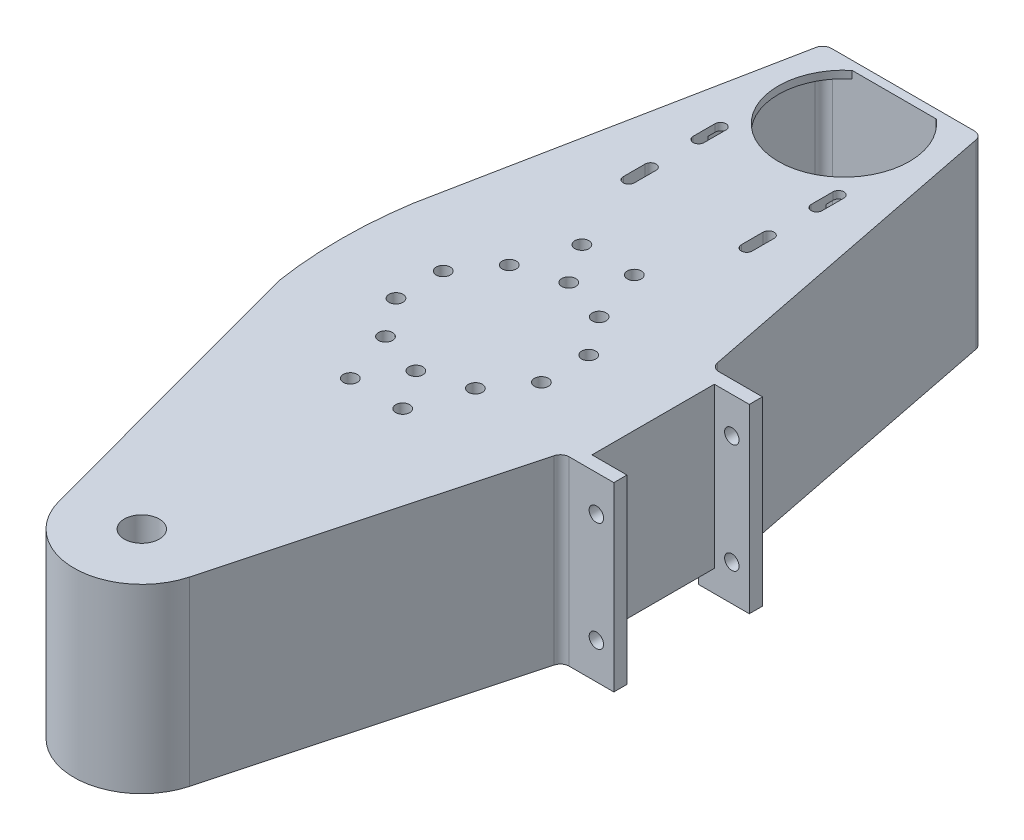
SolidWorks part; units mm, degrees
material "POM Acetal Copolymer"
ref_plane "Front" through (0, 0, 0) normal (0, 0, 1) x (1, 0, 0)
ref_plane "Top" through (0, 0, 0) normal (0, 1, 0) x (1, 0, 0)
ref_plane "Right" through (0, 0, 0) normal (1, 0, 0) x (0, 0, -1)
sketch "Sketch1" plane through (0, 0, 0) normal (0, 1, 0) x (1, 0, 0)
  line L0 (-33.537, -15.3371) -> (-14.9662, -84.2577)
  line L1 (0, 0) -> (0, -80.225) construction
  line L2 (33.4435, -15.54) -> (14.9683, -84.2498)
  line L3 (0, 0) -> (-34.71, 0.0224) construction
  line L4 (33.5879, 15.2256) -> (18, 93.9634)
  line L5 (-18, 93.9634) -> (-33.5171, 15.3805)
  line L6 (0, 0) -> (0, 93.9634) construction
  line L7 (18, 93.9634) -> (-18, 93.9634)
  arc A0 (18.2929, 50.0161) -> (0, 50.8542) centre (0, -149.2091) ccw construction
  arc A1 (-17.551, -50.0828) -> (0, -50.8542) centre (0, 149.2092) ccw construction
  arc A2 (0, -50.8542) -> (17.2848, -50.1061) centre (0, 149.2092) ccw construction
  arc A3 (18.2929, 50.0161) -> (0, 50.8542) centre (0, -149.2091) ccw construction
  arc A4 (-17.551, -50.0828) -> (0, -50.8542) centre (0, 149.2092) ccw construction
  arc A5 (0, -50.8542) -> (17.2848, -50.1061) centre (0, 149.2092) ccw construction
  arc A6 (33.5879, 15.2256) -> (33.4435, -15.54) centre (-64.9013, 0.3045) cw
  arc A7 (-33.5171, 15.3805) -> (-33.537, -15.3371) centre (65.5838, -0.0425) ccw
  arc A8 (-14.9662, -84.2577) -> (14.9683, -84.2498) centre (0, -80.225) ccw
  spline S0 degree 3 poles (207379.7461, -62473.6529) (41124.2315, -9853.6275) (501.3421, 1649.4917) (-356.7314, -965.2424) (14589.6274, -6960.5386) (204631.7384, -70260.9784) knots -155.187346 -155.187346 -155.187346 -155.187346 0.5 0.5 96.391343 96.391343 96.391343 96.391343 only from (-23.3099, 46.5686) to (-33.5171, 15.3805) construction
  spline S1 degree 3 poles (50438.7177, -210724.222) (5852.5985, -22210.9996) (278.0412, 155.9422) (-20.0063, 49.5893) (-20.2555, 49.4821) (-20.7338, 49.2401) (-20.9643, 49.1048) (-21.6305, 48.6558) (-22.0429, 48.2951) (-22.5763, 47.6956) (-22.7414, 47.4851) (-77.3694, -31.9423) (1466.9665, -1620.8682) (131582.8299, 171386.3608) knots -145.973282 -145.973282 -145.973282 -145.973282 0.25 0.25 0.375 0.375 0.5 0.5 0.75 0.75 0.875 0.875 45.624506 45.624506 45.624506 45.624506 only from (-18.1778, 50.0274) to (-23.3099, 46.5686) construction
  spline S2 degree 3 poles (19111.3364, -215570.3104) (-164.665, 71819.1846) (-6391.5375, 72306.8257) (535.0409, -216401.0405) knots -510.789358 -510.789358 -510.789358 -510.789358 511.094551 511.094551 511.094551 511.094551 only from (0, 50.8542) to (-18.1778, 50.0274) construction
  spline S3 degree 3 poles (-172858.9775, -130437.1942) (-9588.4932, -7736.2031) (176.4823, -125.8053) (22.3381, 48.0777) (22.1448, 48.27) (21.7383, 48.6261) (21.3129, 48.9538) (20.8504, 49.2262) (20.3689, 49.4702) (20.1181, 49.578) (-205.1622, 130.0412) (-3769.6033, -12503.7613) (-55697.9815, -209273.9216) knots -107.676945 -107.676945 -107.676945 -107.676945 0.25 0.25 0.375 0.375 0.5 0.625 0.625 0.75 0.75 111.7454 111.7454 111.7454 111.7454 only from (23.4249, 46.5486) to (18.2929, 50.0161) construction
  spline S4 degree 3 poles (-204829.9693, -69714.8134) (-14410.063, -6839.0217) (351.3401, -956.9696) (-508.7388, 1686.3527) (-43184.1858, -10330.2422) (-207542.4345, -61827.7492) knots -94.178272 -94.178272 -94.178272 -94.178272 0.5 0.5 159.057484 159.057484 159.057484 159.057484 only from (33.5879, 15.2256) to (23.4249, 46.5486) construction
  spline S5 degree 3 poles (204920.3333, 69372.6046) (14851.4813, 6986.492) (-354.7334, 974.1995) (506.994, -1691.7686) (43263.1864, 10258.5586) (207658.4047, 61423.9901) knots -98.095203 -98.095203 -98.095203 -98.095203 0.5 0.5 163.390786 163.390786 163.390786 163.390786 only from (-33.537, -15.3371) to (-23.6739, -45.931) construction
  spline S6 degree 3 poles (173677.1656, 129335.7077) (10958.7849, 8735.7397) (-200.2335, 154.5977) (-22.3843, -47.7664) (-22.1539, -47.9973) (-21.6694, -48.4243) (-21.1617, -48.8172) (-20.6088, -49.1434) (-20.0327, -49.4356) (-19.733, -49.5642) (224.4992, -136.4917) (3799.4756, 12385.73) (56045.5899, 209143.2387) knots -104.372656 -104.372656 -104.372656 -104.372656 0.25 0.25 0.375 0.375 0.5 0.625 0.625 0.75 0.75 101.44206 101.44206 101.44206 101.44206 only from (-23.6739, -45.931) to (-17.551, -50.0828) construction
  spline S7 degree 3 poles (-55530.9156, 209321.4463) (-3779.5935, 12434.495) (-225.4106, -135.9571) (19.4564, -49.5951) (19.7548, -49.4682) (20.3288, -49.1797) (20.88, -48.8574) (21.3866, -48.469) (21.8705, -48.0469) (22.101, -47.8184) (196.9698, 148.8582) (-10389.8216, 8391.4062) (-172964.2918, 130271.9782) knots -101.143646 -101.143646 -101.143646 -101.143646 0.25 0.25 0.375 0.375 0.5 0.625 0.625 0.75 0.75 103.482751 103.482751 103.482751 103.482751 only from (17.2848, -50.1061) to (23.3954, -46.0009) construction
  spline S8 degree 3 poles (-207355.5254, 62554.6676) (-48310.3254, 12031.7671) (-549.3929, -1781.6745) (357.4779, 960.0169) (-14502.7986, 6961.3262) (-204454.2979, 70720.1623) knots -171.948312 -171.948312 -171.948312 -171.948312 0.5 0.5 98.144902 98.144902 98.144902 98.144902 only from (23.3954, -46.0009) to (33.4435, -15.54) construction
  spline S9 degree 3 poles (-23.3099, 46.5686) (-25.8451, 41.6435) (-27.964, 36.5822) (-31.3748, 26.1889) (-32.6649, 20.8563) (-33.5171, 15.3805) knots 0 0 0 0 0.5 0.5 1 1 1 1 construction
  spline S10 degree 3 poles (-18.1778, 50.0274) (-18.718, 49.9778) (-19.2426, 49.8618) (-20.0063, 49.5893) (-20.2555, 49.4821) (-20.7338, 49.2401) (-20.9643, 49.1048) (-21.6305, 48.6558) (-22.0429, 48.2951) (-22.5763, 47.6956) (-22.7414, 47.4851) (-23.0457, 47.0426) (-23.1854, 46.8095) (-23.3099, 46.5686) knots 0 0 0 0 0.25 0.25 0.375 0.375 0.5 0.5 0.75 0.75 0.875 0.875 1 1 1 1 construction
  spline S11 degree 3 poles (0, 50.8542) (-6.0718, 50.8544) (-12.1311, 50.5788) (-18.1778, 50.0274) knots 0 0 0 0 1 1 1 1 construction
  spline S12 degree 3 poles (23.4249, 46.5486) (23.1764, 47.0321) (22.873, 47.4743) (22.3381, 48.0777) (22.1448, 48.27) (21.7383, 48.6261) (21.3129, 48.9538) (20.8504, 49.2262) (20.3689, 49.4702) (20.1181, 49.578) (19.3579, 49.8495) (18.8341, 49.966) (18.2929, 50.0161) knots 0 0 0 0 0.25 0.25 0.375 0.375 0.5 0.625 0.625 0.75 0.75 1 1 1 1 construction
  spline S13 degree 3 poles (33.5879, 15.2256) (32.7546, 20.7253) (31.4771, 26.0809) (28.0808, 36.5191) (25.9636, 41.6022) (23.4249, 46.5486) knots 0 0 0 0 0.5 0.5 1 1 1 1 construction
  spline S14 degree 3 poles (-33.537, -15.3371) (-32.7089, -20.6991) (-31.4605, -25.9256) (-28.1651, -36.121) (-26.1195, -41.0904) (-23.6739, -45.9309) knots 0 0 0 0 0.5 0.5 0.999996 0.999996 0.999996 0.999996 construction
  spline S15 degree 3 poles (-23.6739, -45.9309) (-23.3808, -46.511) (-23.0211, -47.0419) (-22.3843, -47.7664) (-22.1539, -47.9973) (-21.6694, -48.4243) (-21.1617, -48.8172) (-20.6088, -49.1434) (-20.0327, -49.4356) (-19.733, -49.5642) (-18.8246, -49.8875) (-18.1984, -50.0254) (-17.551, -50.0828) knots -0.000018 -0.000018 -0.000018 -0.000018 0.25 0.25 0.375 0.375 0.5 0.625 0.625 0.75 0.75 1 1 1 1 construction
  spline S16 degree 3 poles (17.2848, -50.1061) (17.9287, -50.0499) (18.5518, -49.9142) (19.4564, -49.5951) (19.7548, -49.4682) (20.3288, -49.1797) (20.88, -48.8574) (21.3866, -48.469) (21.8705, -48.0469) (22.101, -47.8184) (22.7388, -47.1011) (23.1003, -46.5751) (23.3959, -45.9998) knots 0 0 0 0 0.25 0.25 0.375 0.375 0.5 0.625 0.625 0.75 0.75 1.000155 1.000155 1.000155 1.000155 construction
  spline S17 degree 3 poles (23.3959, -45.9998) (25.8693, -41.1869) (27.9446, -36.2426) (31.3021, -26.0921) (32.5827, -20.8853) (33.4435, -15.54) knots 0.000037 0.000037 0.000037 0.000037 0.5 0.5 1 1 1 1 construction
  dimension "D1" = 80.225
  dimension "D3" = 93.975
  dimension "D2" = 15.5
  dimension "D4" = 36
extrude "Boss-Extrude1" add sketch "Sketch1" along normal blind 41.5
sketch "Sketch2" plane through (0, 0, 0) normal (0, 1, 0) x (1, 0, 0)
  circle A0 centre (0, 0) radius 36
  dimension "D1" = 72
extrude "Cut-Extrude1" cut sketch "Sketch2" along normal blind 5
sketch "Sketch4" plane through (0, 0, 0) normal (0, 1, 0) x (1, 0, 0)
  circle A0 centre (0, 0) radius 20.15
  dimension "D1" = 40.3
extrude "Cut-Extrude3" cut sketch "Sketch4" along normal blind 32
sketch "Sketch6" plane through (0, 0, 0) normal (0, -1, 0) x (1, 0, 0)
  line L0 (18, -93.9634) -> (-18, -93.9634) construction
  line L1 (-16.15, -36.1634) -> (16.15, -36.1634)
  line L2 (-16.15, -36.1634) -> (-16.15, -91.9634)
  line L3 (-16.15, -91.9634) -> (16.15, -91.9634)
  line L4 (16.15, -36.1634) -> (16.15, -91.9634)
  line L5 (-16.15, -36.1634) -> (16.15, -91.9634) construction
  line L6 (-16.15, -91.9634) -> (16.15, -36.1634) construction
  point P0 (0, -64.0634)
  point P6 (0, -91.9634)
  dimension "D1" = 2
  dimension "D2" = 55.8
  dimension "D3" = 32.3
extrude "Cut-Extrude5" cut sketch "Sketch6" against normal blind 39.8
sketch "Sketch7" plane through (0, 0, 0) normal (0, 1, 0) x (1, 0, 0)
  line L0 (16.15, 36.1634) -> (-16.15, 36.1634) construction
  line L1 (-16.15, 91.9634) -> (16.15, 91.9634) construction
  line L3 (9.6307, 91.9634) -> (-9.6307, 91.9634)
  arc A0 (9.6307, 91.9634) -> (-9.6307, 91.9634) centre (0, 80.4634) ccw construction
  arc A1 (-9.6307, 91.9634) -> (9.6307, 91.9634) centre (0, 80.4634) ccw
  dimension "D1" = 44.3
  dimension "D2" = 30
extrude "Cut-Extrude6" cut sketch "Sketch7" along normal through all and the other way through all
sketch "Sketch8" plane through (0, 0, 0) normal (0, 1, 0) x (1, 0, 0)
  line L0 (0, 0) -> (-30.54, -11.1157)
  line L1 (0, 0) -> (30.54, -11.1157)
  line L2 (0, 0) -> (0, 32.5) construction
  circle A0 centre (0, 0) radius 23
  circle A1 centre (0, 0) radius 32.5
  dimension "D1" = 46
  dimension "D2" = 65
  dimension "D3" = 220
extrude "Cut-Extrude7" cut sketch "Sketch8" along normal blind 38.5 contours A0 L2 A1 L0 | L2 A0 L1 A1 region at (-19.5872, 0, -13.7151) region at (19.5872, 0, -13.7151)
sketch "Sketch12" plane through (0, 5, 0) normal (0, -1, 0) x (1, 0, 0)
  circle A0 centre (0, 0) radius 32.5
  arc A1 (-30.54, 11.1157) -> (30.54, 11.1157) centre (0, 0) ccw construction
extrude "Cut-Extrude10" cut sketch "Sketch12" against normal blind 6
sketch "Sketch9" plane through (0, 11, 0) normal (0, -1, 0) x (1, 0, 0)
  line L0 (0, 0) -> (0, 20.15) construction
  line L1 (-3, 24.8193) -> (-2.5, 19.9943)
  line L2 (3, 24.8193) -> (2.5, 19.9943)
  circle A0 centre (0, 0) radius 20.15 construction
  arc A1 (2.5, 19.9943) -> (-2.5, 19.9943) centre (0, 0) ccw
  arc A2 (3, 24.8193) -> (-3, 24.8193) centre (0, 0) ccw
  circle A3 centre (0, 0) radius 20.15 construction
  point P14 (0, 20.15)
  dimension "D1" = 5
  dimension "D3" = 25
  dimension "D2" = 6
extrude "Boss-Extrude2" add sketch "Sketch9" along normal blind 5
sketch "Sketch10" plane through (0, 0, 0) normal (0, 1, 0) x (1, 0, 0)
  line L0 (16.15, 36.1634) -> (-16.15, 36.1634) construction
  line L1 (16.15, 36.1634) -> (-16.15, 36.1634)
  line L2 (-10, 34.5832) -> (-10, 36.1634)
  line L3 (-18, 93.9634) -> (-33.5171, 15.3805)
  line L4 (18, 93.9634) -> (-18, 93.9634)
  line L5 (18, 93.9634) -> (-18, 93.9634)
  line L6 (-18, 93.9634) -> (-33.5171, 15.3805)
  line L7 (33.5879, 15.2256) -> (18, 93.9634)
  line L8 (33.5879, 15.2256) -> (18, 93.9634)
  line L9 (10, 34.5832) -> (10, 36.1634)
  line L10 (0, 0) -> (0, 20.15) construction
  line L11 (-10, 34.5832) -> (-10, 20.7123)
  line L12 (10, 34.5832) -> (10, 20.7123)
  line L13 (10, 20.7123) -> (-10, 20.7123)
  arc A1 (-21.6129, 7.8665) -> (-21.6129, -7.8665) centre (0, 0) ccw construction
  arc A2 (-21.6129, 7.8665) -> (-21.6129, -7.8665) centre (0, 0) ccw
  arc A3 (34.0638, 11.6471) -> (-34.007, 11.8121) centre (0, 0) ccw
  arc A4 (-33.5171, 15.3805) -> (-34.007, 11.8121) centre (65.5838, -0.0425) ccw
  arc A5 (34.0638, 11.6471) -> (33.5879, 15.2256) centre (-64.9013, 0.3045) ccw
  arc A6 (34.0638, 11.6471) -> (-34.007, 11.8121) centre (0, 0) ccw
  arc A7 (-33.5171, 15.3805) -> (-34.007, 11.8121) centre (65.5838, -0.0425) ccw
  arc A8 (34.0638, 11.6471) -> (33.5879, 15.2256) centre (-64.9013, 0.3045) ccw
  arc A9 (2.5, -19.9943) -> (-2.5, -19.9943) centre (0, 0) ccw construction
  dimension "D2" = 20
  dimension "D1" = 0
extrude "Cut-Extrude8" cut sketch "Sketch10" along normal blind 10 contours A6 L9 L1 L2 | L12 A6 L11 A2 | L2 region at (9.7994, 0, -35.3733) region at (0, 0, -28.1279)
sketch "Sketch11" plane through (0, 41.5, 0) normal (0, 1, 0) x (1, 0, 0)
  circle A0 centre (0, 0) radius 17.5 construction
  circle A1 centre (0, 17.5) radius 1.6
  circle A2 centre (10.2862, 14.1578) radius 1.6
  circle A3 centre (16.6435, 5.4078) radius 1.6
  circle A4 centre (16.6435, -5.4078) radius 1.6
  circle A5 centre (10.2862, -14.1578) radius 1.6
  circle A6 centre (0, -17.5) radius 1.6
  circle A7 centre (-10.2862, -14.1578) radius 1.6
  circle A8 centre (-16.6435, -5.4078) radius 1.6
  circle A9 centre (-16.6435, 5.4078) radius 1.6
  circle A10 centre (-10.2862, 14.1578) radius 1.6
  point P25 (0, 0)
  dimension "D1" = 35
  dimension "D2" = 3.2
  dimension "D3" = 10
extrude "Cut-Extrude9" cut sketch "Sketch11" against normal through all and the other way through all
sketch "Sketch13" plane through (0, 39.8, 0) normal (0, -1, 0) x (1, 0, 0)
  line L1 (-16.15, -36.1634) -> (-10, -36.1634)
  line L2 (-16.15, -36.1634) -> (-16.15, -64.1634)
  line L3 (-16.15, -64.1634) -> (-10, -64.1634)
  line L4 (-10, -36.1634) -> (-10, -64.1634)
  line L5 (16.15, -36.1634) -> (10, -36.1634)
  line L6 (16.15, -36.1634) -> (16.15, -64.1634)
  line L7 (16.15, -64.1634) -> (10, -64.1634)
  line L8 (10, -36.1634) -> (10, -64.1634)
  line L9 (-10, -36.1634) -> (10, -36.1634)
  line L10 (-10, -36.1634) -> (-10, -41.1634)
  line L11 (-10, -41.1634) -> (10, -41.1634)
  line L12 (10, -36.1634) -> (10, -41.1634)
  line M8 (16.15, -91.9634) -> (16.15, -36.1634)
  line M9 (16.15, -36.1634) -> (-16.15, -36.1634)
  line M10 (-16.15, -36.1634) -> (-16.15, -91.9634)
  dimension "D1" = 20
  dimension "D2" = 28
  dimension "D3" = 5
extrude "Boss-Extrude3" add sketch "Sketch13" along normal blind 3 contours L4 L3 M9 M10 | L4 L11 L8 M9 | L8 L7 M9 M8 region at (-13.075, 39.8, -50.1634) region at (0, 39.8, -38.6634) region at (13.075, 39.8, -50.1634)
sketch "Sketch14" plane through (0, 41.5, 0) normal (0, 1, 0) x (1, 0, 0)
  line L0 (0, 0) -> (0, 93.9634) construction
  line L1 (18, 93.9634) -> (-18, 93.9634) construction
  line L2 (-13.5, 93.9634) -> (-13.5, 44.4734) construction
  line L3 (-13.5, 44.4734) -> (13.5, 44.4734) construction
  line L4 (13.5, 44.4734) -> (13.5, 93.9634) construction
  line L5 (-13.5, 65.7234) -> (-13.5, 60.7234) construction
  line L6 (-12.25, 65.7234) -> (-12.25, 60.7234)
  line L7 (-14.75, 65.7234) -> (-14.75, 60.7234)
  line L8 (-13.5, 49.7234) -> (-13.5, 44.7234) construction
  line L9 (-12.25, 49.7234) -> (-12.25, 44.7234)
  line L10 (-14.75, 49.7234) -> (-14.75, 44.7234)
  line L11 (13.5, 65.7234) -> (13.5, 60.7234) construction
  line L12 (14.75, 65.7234) -> (14.75, 60.7234)
  line L13 (12.25, 65.7234) -> (12.25, 60.7234)
  line L14 (13.5, 49.7234) -> (13.5, 44.7234) construction
  line L15 (14.75, 49.7234) -> (14.75, 44.7234)
  line L16 (12.25, 49.7234) -> (12.25, 44.7234)
  circle A0 centre (-13.5, 65.7234) radius 1.25
  circle A1 centre (-13.5, 49.7234) radius 1.25
  arc A2 (-12.25, 65.7234) -> (-14.75, 65.7234) centre (-13.5, 65.7234) ccw
  arc A3 (-14.75, 60.7234) -> (-12.25, 60.7234) centre (-13.5, 60.7234) ccw
  circle A4 centre (13.5, 49.7234) radius 1.25
  circle A5 centre (13.5, 65.7234) radius 1.25
  arc A6 (-12.25, 49.7234) -> (-14.75, 49.7234) centre (-13.5, 49.7234) ccw
  arc A7 (-14.75, 44.7234) -> (-12.25, 44.7234) centre (-13.5, 44.7234) ccw
  arc A8 (14.75, 65.7234) -> (12.25, 65.7234) centre (13.5, 65.7234) ccw
  arc A9 (12.25, 60.7234) -> (14.75, 60.7234) centre (13.5, 60.7234) ccw
  arc A10 (14.75, 49.7234) -> (12.25, 49.7234) centre (13.5, 49.7234) ccw
  arc A11 (12.25, 44.7234) -> (14.75, 44.7234) centre (13.5, 44.7234) ccw
  point P13 (-13.5, 63.2234)
  point P23 (-13.5, 47.2234)
  point P29 (13.5, 63.2234)
  point P35 (13.5, 47.2234)
  dimension "D3" = 2.5
  dimension "D1" = 27
  dimension "D2" = 49.49
  dimension "D4" = 28.24
  dimension "D5" = 16
  dimension "D6" = 5
extrude "Cut-Extrude11" cut sketch "Sketch14" against normal through all contours L9 A7 L10 A6 | L6 A3 L7 A2 | L12 A9 L13 A8 | L15 A11 L16 A10
sketch "Sketch15" plane through (0, 0, 0) normal (0, 1, 0) x (1, 0, 0)
  line L0 (9.7836, -20.981) -> (0, 0) construction
  line L1 (-9.7836, -20.981) -> (0, 0) construction
  line L2 (-17.6977, -9.634) -> (-29.3836, -13.8873)
  line L3 (-30.54, -11.1157) -> (-21.6129, -7.8665) construction
  line L4 (0, 0) -> (12.2676, -19.6323) construction
  line L5 (0, 0) -> (-12.2676, -19.6323) construction
  line L6 (17.6977, -9.634) -> (29.3836, -13.8873)
  line L7 (-0.3306, -73.2328) -> (-10.394, -35.885)
  line L8 (1.5, -73.3876) -> (-1.5, -73.3876)
  line L9 (-2.5, -19.9943) -> (-3, -24.8193)
  line L10 (13.35, -78.725) -> (-13.35, -78.725)
  line L11 (3, -24.8193) -> (2.5, -19.9943)
  line L12 (-2.5, -19.9943) -> (-3, -24.8193)
  line L13 (3, -24.8193) -> (2.5, -19.9943)
  line L14 (1.5, -73.3876) -> (1.5, -92.725)
  line L15 (1.5, -92.725) -> (-1.5, -92.725)
  line L16 (-1.5, -73.3876) -> (-1.5, -92.725)
  line L17 (1.5, -73.3876) -> (-1.5, -92.725) construction
  line L18 (1.5, -92.725) -> (-1.5, -73.3876) construction
  line L19 (13.35, -78.725) -> (13.35, -81.725)
  line L20 (13.35, -81.725) -> (-13.35, -81.725)
  line L21 (-13.35, -78.725) -> (-13.35, -81.725)
  line L22 (13.35, -78.725) -> (-13.35, -81.725) construction
  line L23 (13.35, -81.725) -> (-13.35, -78.725) construction
  line L24 (-0.3306, -73.2328) -> (-3.2272, -74.0133)
  line L25 (-10.394, -35.885) -> (-13.2907, -36.6655)
  line L26 (-3.2272, -74.0133) -> (-13.2907, -36.6655)
  line L27 (-0.3306, -73.2328) -> (-13.2907, -36.6655) construction
  line L28 (-10.394, -35.885) -> (-3.2272, -74.0133) construction
  line L29 (0, -80.225) -> (-11.5823, -37.2404) construction
  line L30 (0.3306, -73.2328) -> (3.2272, -74.0133)
  line L31 (-30.6403, -14.5566) -> (-12.0695, -83.4772)
  line L32 (12.0712, -83.4708) -> (30.5464, -14.761)
  line L33 (-26.9724, -28.1689) -> (-12.0695, -83.4772)
  line L34 (12.0712, -83.4708) -> (26.9304, -28.2091)
  line L35 (0.3306, -73.2328) -> (10.394, -35.885)
  line L36 (10.394, -35.885) -> (13.2907, -36.6655)
  line L37 (3.2272, -74.0133) -> (13.2907, -36.6655)
  line L38 (-9.7836, -20.981) -> (-13.7351, -29.455)
  line L39 (-12.2676, -19.6323) -> (-17.2224, -27.5616)
  line L40 (12.2676, -19.6323) -> (17.2224, -27.5616)
  line L41 (9.7836, -20.981) -> (13.7351, -29.455)
  line L42 (30.645, 14.643) -> (15.0571, 93.3808)
  line L43 (28.2133, 26.926) -> (19.15, 72.7067)
  line L45 (-15.0568, 93.3822) -> (-30.5739, 14.7993)
  line L46 (-19.15, 72.6533) -> (-28.1705, 26.9707)
  line L56 (-19.15, 36.1634) -> (-19.15, 91.9634)
  line L57 (-19.15, 33.9747) -> (-19.15, 72.6533)
  line L59 (19.15, 91.9634) -> (19.15, 36.1634)
  line L60 (19.15, 72.7067) -> (19.15, 33.9747)
  line L64 (0, 0) -> (0, -80.225) construction
  circle A0 centre (0, -80.225) radius 4
  circle A1 centre (0, -80.225) radius 7
  arc A2 (-3, -24.8193) -> (3, -24.8193) centre (0, 0) ccw
  arc A3 (-2.5, -19.9943) -> (2.5, -19.9943) centre (0, 0) ccw
  arc A4 (-3, -24.8193) -> (3, -24.8193) centre (0, 0) ccw
  arc A5 (-2.5, -19.9943) -> (2.5, -19.9943) centre (0, 0) ccw
  circle A6 centre (0, 0) radius 20.15 construction
  arc A7 (-30.54, -11.1157) -> (30.54, -11.1157) centre (0, 0) ccw construction
  arc A8 (-17.6977, -9.634) -> (17.6977, -9.634) centre (0, 0) ccw
  arc A9 (-30.54, -11.1157) -> (30.54, -11.1157) centre (0, 0) ccw
  arc A10 (-20.5444, -10.6701) -> (20.5444, -10.6701) centre (0, 0) ccw
  circle A11 centre (0, 0) radius 23.15 construction
  circle A12 centre (0, 0) radius 20.15 construction
  arc A18 (-12.0695, -83.4772) -> (12.0712, -83.4708) centre (0, -80.225) ccw
  arc A19 (-12.0695, -83.4772) -> (12.0712, -83.4708) centre (0, -80.225) ccw
  arc A29 (-36.8575, -12.7486) -> (36.7825, -12.9634) centre (0, 0) ccw
  arc A30 (-26.9724, -28.1689) -> (26.9304, -28.2091) centre (0, 0) ccw
  arc A36 (36.9025, 12.6177) -> (10.8333, 37.4652) centre (0, 0) ccw
  arc A37 (28.2133, 26.926) -> (19.15, 33.9747) centre (0, 0) ccw
  arc A39 (-10.8333, 37.4652) -> (-36.8409, 12.7964) centre (0, 0) ccw
  arc A40 (-19.15, 33.9747) -> (-28.1705, 26.9707) centre (0, 0) ccw
  point P54 (0, -83.0563)
  point P75 (-6.8106, -54.9491)
  dimension "D15" = 8
  dimension "D12" = 50
  dimension "D16" = 3
  dimension "D18" = 3
  dimension "D19" = 3
  dimension "D9" = 3
  dimension "D11" = 7
  dimension "D1" = 3
  dimension "D2" = 3
  dimension "D3" = 3
  dimension "D4" = 3
  dimension "D5" = 3
  dimension "D6" = 3
  dimension "D7" = 3
  dimension "D8" = 3
  dimension "D14" = 0
  dimension "D17" = 3
  dimension "D10" = 3
extrude "Cut-Extrude12" cut sketch "Sketch15" along normal offset from surface (38.5 mm away) 3 contours A37 L43 L60 | A40 L57 L46 | L13 A4 L12 | A30 L33 L10 A1 L26 | A30 L7 A1 L35 | A30 L37 A1 L10 L34 | L14 A19 L34 L20 A1 | L33 A19 L16 A1 L20 | L10 A0 L14 | L14 A0 L16 L10 | L16 A0 L10 | L10 A0 L20 L16 | L20 A0 L10 L14 | L20 L14 L10 L16 | L14 A0 L20 | L16 A0 L14 L20 | L20 A0 L16 | A10 L40 A9 L6 | A10 L2 A9 L39 region at (-20.6219, 0, 18.6075) region at (0, 0, 27.3623) region at (20.6219, 0, 18.6075) region at (0, 0, 50.5135) region at (-14.2487, 0, 55.3133) region at (14.2354, 0, 55.3285) region at (0, 0, 77.5214) region at (-2.3343, 0, 77.8907) region at (2.3343, 0, 77.8907) region at (-2.7036, 0, 80.225) region at (0, 0, 80.225) region at (-6.6579, 0, 86.8709) region at (2.7036, 0, 80.225) region at (0, 0, 82.9286) region at (-2.3343, 0, 82.5593) region at (6.6578, 0, 86.871) region at (2.3343, 0, 82.5593) region at (22.1406, 0, -44.7994) region at (-22.1268, 0, -44.7934) up to face at (-13.5, 41.5, -63.2234)
extrude "Cut-Extrude13" cut sketch "Sketch15<3>" against normal through all and the other way through all contours L16 A0 L14 L20 | L20 L14 L10 L16 | L20 A0 L10 L14 | L14 A0 L20 | L10 A0 L14 | L14 A0 L16 L10 | L10 A0 L20 L16 | L20 A0 L16 | L16 A0 L10 region at (0, 0, 77.5214) region at (-2.3343, 0, 77.8907) region at (2.3343, 0, 77.8907) region at (-2.7036, 0, 80.225) region at (0, 0, 80.225) region at (2.7036, 0, 80.225) region at (0, 0, 82.9286) region at (-2.3343, 0, 82.5593) region at (2.3343, 0, 82.5593)
sketch "Sketch15<3>" plane through (0, 0, 0) normal (0, 1, 0) x (1, 0, 0) same geometry as "Sketch15"
sketch "Sketch16" plane through (0, 0, 0) normal (0, 1, 0) x (1, 0, 0)
  line L1 (-6, 26.5) -> (6, 26.5) construction
  line L2 (-6, 26.5) -> (-6, -26.5) construction
  line L3 (-6, -26.5) -> (6, -26.5) construction
  line L4 (6, 26.5) -> (6, -26.5) construction
  line L5 (-6, 26.5) -> (6, -26.5) construction
  line L6 (-6, -26.5) -> (6, 26.5) construction
  circle A0 centre (6, -26.5) radius 1.6
  circle A1 centre (-6, -26.5) radius 1.6
  circle A2 centre (-6, 26.5) radius 1.6
  circle A3 centre (6, 26.5) radius 1.6
  point P0 (0, 0)
  dimension "D3" = 3.2
  dimension "D1" = 53
  dimension "D2" = 12
extrude "Cut-Extrude14" cut sketch "Sketch16" against normal through all and the other way through all
sketch "Sketch22" plane through (0, 6, 0) normal (0, -1, 0) x (1, 0, 0)
  line L0 (0, 20.15) -> (0, 25) construction
  line L2 (-3, 24.8193) -> (-2.5, 19.9943)
  line L3 (2.5, 19.9943) -> (3, 24.8193)
  line L4 (-3, 24.8193) -> (-2.5, 19.9943)
  line L5 (2.5, 19.9943) -> (3, 24.8193)
  circle A0 centre (0, 22.575) radius 1
  arc A2 (3, 24.8193) -> (-3, 24.8193) centre (0, 0) ccw
  arc A3 (2.5, 19.9943) -> (-2.5, 19.9943) centre (0, 0) ccw
  arc A4 (3, 24.8193) -> (-3, 24.8193) centre (0, 0) ccw
  arc A5 (2.5, 19.9943) -> (-2.5, 19.9943) centre (0, 0) ccw
  dimension "D2" = 2
  dimension "D1" = 0
extrude "Cut-Extrude17" cut sketch "Sketch22" against normal blind 24 contours A0
extrude "Cut-Extrude18" cut sketch "Sketch22<3>" against normal blind 5
sketch "Sketch22<3>" plane through (0, 6, 0) normal (0, -1, 0) x (1, 0, 0) same geometry as "Sketch22"
fillet "Fillet1" radius 2 6 edges at (-16.15, 18.4, -36.1634) (16.15, 18.4, -36.1634) (-16.15, 19.9, -91.9634) (16.15, 19.9, -91.9634) (18, 20.75, -93.9634) (-18, 20.75, -93.9634)
fillet "Fillet2" radius 1 52 edges at (3, 24.75, 24.8193) (-3, 24.75, 24.8193) (21.6129, 24.75, 7.8665) (30.54, 24.75, 11.1157) (-30.54, 24.75, 11.1157) (-21.6129, 24.75, 7.8665) (-9.8988, 19.25, 37.7229) (9.8988, 19.25, 37.7229) (-26.9724, 19.25, 28.1689) (-13.2907, 19.25, 36.6655) (-3.2272, 19.25, 74.0133) (-6.8374, 19.25, 78.725) (-13.35, 19.25, 78.725) (-12.5416, 19.25, 81.725) (-6.8374, 19.25, 81.725) (-1.5, 19.25, 87.0624) (-1.5, 19.25, 92.6347) (1.5, 19.25, 92.6347) (1.5, 19.25, 87.0624) (6.8374, 19.25, 81.725) (12.5407, 19.25, 81.725) (13.3473, 19.25, 78.725) (6.8374, 19.25, 78.725) (3.2272, 19.25, 74.0133) (13.2907, 19.25, 36.6655) (26.9304, 19.25, 28.2091) (19.15, 19.25, -33.9747) (28.2133, 19.25, -26.926) (19.15, 19.25, -72.7067) (-19.15, 19.25, -72.6533) (-28.1705, 19.25, -26.9707) (-19.15, 19.25, -33.9747) (10, 7.5, -30.9233) (-10, 7.5, -30.9233) (-16.15, 38.3, -64.1634) (-10, 38.3, -64.1634) (10, 38.3, -64.1634) (16.15, 38.3, -64.1634) (-10, 38.3, -41.1634) (10, 38.3, -41.1634) (-9.7836, 24.75, 20.981) (-13.7351, 24.75, 29.455) (-17.2224, 24.75, 27.5616) (-12.2676, 24.75, 19.6323) (-20.5444, 24.75, 10.6701) (-29.3836, 24.75, 13.8873) (9.7836, 24.75, 20.981) (13.7351, 24.75, 29.455) (20.5444, 24.75, 10.6701) (29.3836, 24.75, 13.8873) (12.2676, 24.75, 19.6323) (17.2224, 24.75, 27.5616)
sketch "Sketch19" plane through (0, 41.5, 0) normal (0, 1, 0) x (1, 0, 0)
  line L0 (33.2366, 17) -> (44.8106, 17)
  line L1 (0, 0) -> (44.8106, 0) construction
  line L2 (44.8106, -17) -> (33.0509, -17)
  line L3 (44.8106, -17) -> (44.8106, -14)
  line L4 (44.8106, 14) -> (44.8106, 17)
  line L5 (33.5879, 15.2256) -> (18.3191, 92.3518)
  line L6 (16.3571, 93.9634) -> (-16.3563, 93.9634)
  line L7 (-18.3184, 92.3508) -> (-33.5171, 15.3805)
  line L8 (-33.537, -15.3371) -> (-14.9662, -84.2577)
  line L9 (14.9683, -84.2498) -> (33.4435, -15.54)
  line L10 (33.5879, 15.2256) -> (18.3191, 92.3518) construction
  line L11 (16.3571, 93.9634) -> (-16.3563, 93.9634)
  line L12 (-18.3184, 92.3508) -> (-33.5171, 15.3805)
  line L13 (-33.537, -15.3371) -> (-14.9662, -84.2577)
  line L14 (14.9683, -84.2498) -> (33.4435, -15.54)
  line L15 (44.8106, -14) -> (33.6793, -14)
  line L16 (44.8106, 14) -> (33.7657, 14)
  line L17 (33.5879, 15.2256) -> (18.3191, 92.3518)
  line L18 (33.5879, 15.2256) -> (18.3191, 92.3518) construction
  line L19 (33.5879, 15.2256) -> (18.3191, 92.3518)
  line L22 (34.7117, 14) -> (34.7117, -14) construction
  line L23 (36.8117, 14) -> (36.8117, -14)
  arc A0 (33.4435, -15.54) -> (33.953, -11.9662) centre (-64.9013, 0.3045) ccw construction
  arc A5 (18.3191, 92.3518) -> (16.3571, 93.9634) centre (16.3571, 91.9634) ccw
  arc A6 (-16.3563, 93.9634) -> (-18.3184, 92.3508) centre (-16.3563, 91.9634) ccw
  arc A7 (-33.5171, 15.3805) -> (-33.537, -15.3371) centre (65.5838, -0.0425) ccw
  arc A8 (-14.9662, -84.2577) -> (14.9683, -84.2498) centre (0, -80.225) ccw
  arc A9 (33.4435, -15.54) -> (33.5879, 15.2256) centre (-64.9013, 0.3045) ccw
  arc A10 (18.3191, 92.3518) -> (16.3571, 93.9634) centre (16.3571, 91.9634) ccw
  arc A11 (-16.3563, 93.9634) -> (-18.3184, 92.3508) centre (-16.3563, 91.9634) ccw
  arc A12 (-33.5171, 15.3805) -> (-33.537, -15.3371) centre (65.5838, -0.0425) ccw
  arc A13 (-14.9662, -84.2577) -> (14.9683, -84.2498) centre (0, -80.225) ccw
  arc A14 (33.4435, -15.54) -> (33.5879, 15.2256) centre (-64.9013, 0.3045) ccw
  point P25 (34.7106, -0.1628)
  line M35 (33.5879, 15.2256) -> (18.3191, 92.3518)
  line M43 (14.9683, -84.2498) -> (33.4435, -15.54)
  arc M44 (33.4435, -15.54) -> (33.5879, 15.2256) centre (-64.9013, 0.3045) ccw
  dimension "D2" = 3
  dimension "D3" = 10.1
  dimension "D4" = 28
  dimension "D5" = 2.1
  dimension "D1" = 0
extrude "Boss-Extrude5" add sketch "Sketch19" against normal up to surface (36.5 mm away) contours L2 L0 M44 | L2 L3 M43 | L1 L22 M44 | L0 L4 M35 region at (39.1647, 41.5, -15.5119) region at (35.579, 41.5, 0.0827) region at (39.1086, 41.5, 15.5138) up to face at (-0.0041, 5, -11.189)
extrude "Boss-Extrude6" add sketch "Sketch19<5>" against normal up to surface (41.5 mm away) contours L16 L4 L0 M44 | L3 L15 L2 M44 region at (39.1647, 41.5, -15.5119) region at (39.1086, 41.5, 15.5138) up to face at (-22.1314, 0, -42.1549)
sketch "Sketch19<5>" plane through (0, 41.5, 0) normal (0, 1, 0) x (1, 0, 0) same geometry as "Sketch19"
sketch "Sketch20" plane through (0, 0, 0) normal (0, -1, 0) x (1, 0, 0)
  line L1 (-44.8106, -14) -> (44.8106, -14)
  line L2 (-44.8106, -14) -> (-44.8106, 14)
  line L3 (-44.8106, 14) -> (44.8106, 14)
  line L4 (44.8106, -14) -> (44.8106, 14)
  line L5 (-44.8106, -14) -> (44.8106, 14) construction
  line L6 (-44.8106, 14) -> (44.8106, -14) construction
  point P0 (0, 0)
extrude "Cut-Extrude15" cut sketch "Sketch20" against normal up to surface (5 mm away) up to face at (10.0241, 5, -7.9924)
sketch "Sketch21" plane through (0, 0, 0) normal (0, 0, 1) x (1, 0, 0)
  line L0 (40.8106, 41.5) -> (40.8106, 0) construction
  line L1 (44.8106, 41.5) -> (33.0509, 41.5) construction
  line L2 (33.0509, 0) -> (44.8106, 0) construction
  line L3 (44.8106, 0) -> (44.8106, 41.5) construction
  line L4 (40.8106, 20.75) -> (44.8106, 20.75) construction
  circle A0 centre (40.8106, 33.25) radius 1.65
  circle A1 centre (40.8106, 8.25) radius 1.65
  dimension "D2" = 3.3
  dimension "D1" = 4
  dimension "D3" = 25
extrude "Cut-Extrude16" cut sketch "Sketch21" against normal through all and the other way through all
fillet "Fillet3" radius 2 2 edges at (33.2366, 20.75, -17) (33.0509, 20.75, 17)
ref_plane "Plane1" through (27.7999, 0, -16.835) normal (-0.8554, 0, 0.518) x (0, -1, 0)
sketch "Sketch23" plane through (27.7999, 0, -16.835) normal (-0.8554, 0, 0.518) x (0, -1, 0)
  line L0 (-41.5, 1.1313) -> (-41.5, -69.5067) construction
  line L1 (0, -24.4018) -> (0, 5.2048) construction
  line L2 (-41.5, 1.1313) -> (-41.5, -69.5067)
  line L3 (0, -24.4018) -> (0, 5.2048)
  line L4 (0, -4.3687) -> (-41.5, -4.3687) construction
  line L5 (-41.5, 1.1313) -> (0, 1.1313) construction
  line L6 (-41.5, 1.1313) -> (0, 1.1313)
  circle A0 centre (-20.75, -4.3687) radius 3.5
  point P8 (0, 0)
  dimension "D1" = 7
  dimension "D2" = 11
extrude "Cut-Extrude19" cut sketch "Sketch23" against normal blind 10 and the other way blind 2 contours L4 A0 | A0 L4 region at (26.3063, 20.75, -19.3013) region at (24.7674, 20.75, -21.8425)
equation "\"`80\"=82.2774"
equation "\"D1@Sketch15\"=\"D2@Sketch15\""
equation "\"D4@Sketch15\"=\"D2@Sketch15\""
equation "\"D3@Sketch15\"=\"D2@Sketch15\""
equation "\"D8@Sketch15\"=\"D2@Sketch15\""
equation "\"D7@Sketch15\"=\"D2@Sketch15\""
equation "\"D6@Sketch15\"=\"D2@Sketch15\""
equation "\"D5@Sketch15\"=\"D2@Sketch15\""
equation "\"D9@Sketch15\"=\"D2@Sketch15\""
equation "\"D11@Sketch15\"=7"
equation "\"D10@Sketch15\"=\"D2@Sketch15\""
equation "\"D16@Sketch15\"=\"D2@Sketch15\""
equation "\"D17@Sketch15\"=\"D2@Sketch15\""
equation "\"D18@Sketch15\"=\"D2@Sketch15\""
equation "\"D19@Sketch15\"=\"D2@Sketch15\""
